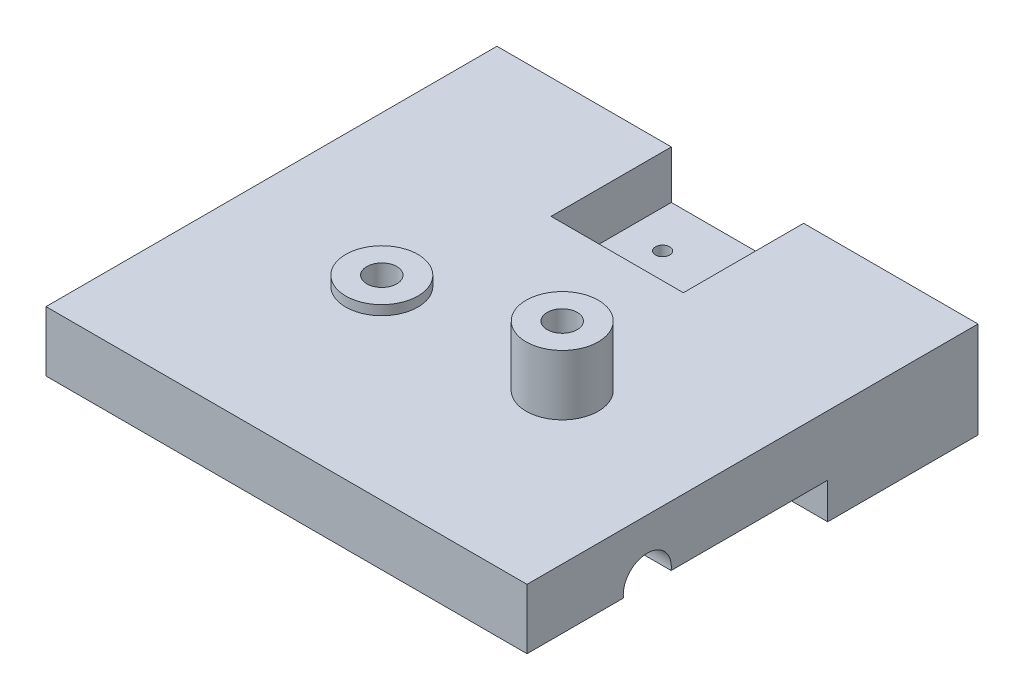
SolidWorks part; units mm, degrees
ref_plane "Front Plane" through (0, 0, 0) normal (0, 0, 1) x (1, 0, 0)
ref_plane "Top Plane" through (0, 0, 0) normal (0, 1, 0) x (1, 0, 0)
ref_plane "Right Plane" through (0, 0, 0) normal (1, 0, 0) x (0, 0, -1)
sketch "Sketch1" plane through (0, 0, 0) normal (0, 1, 0) x (1, 0, 0)
  line L1 (0, 0) -> (80, 0)
  line L2 (0, 0) -> (0, -50)
  line L3 (0, -50) -> (80, -50)
  line L4 (80, 0) -> (80, -50)
  dimension "D1" = 80
  dimension "D2" = 50
extrude "Boss-Extrude1" add sketch "Sketch1" along normal blind 10
sketch "Sketch2" plane through (0, 0, 0) normal (0, 0, 1) x (1, 0, 0)
  line L0 (0, 0) -> (80, 0) construction
  circle A0 centre (14, 0) radius 6.5
  circle A1 centre (66, 0) radius 6.5
  dimension "D1" = 13
  dimension "D2" = 13
  dimension "D3" = 14
  dimension "D4" = 14
extrude "Boss-Extrude3" add sketch "Sketch2" along normal blind 10
sketch "Sketch3" plane through (0, 0, 0) normal (0, 0, -1) x (-1, 0, 0)
  circle A0 centre (-66, 0) radius 6.5
  circle A1 centre (-14, 0) radius 6.5
extrude "Boss-Extrude4" add sketch "Sketch3" along normal blind 15
sketch "Sketch4" plane through (0, 0, -15) normal (0, 0, -1) x (-1, 0, 0)
  circle A0 centre (-14, 0) radius 3.15
  circle A1 centre (-66, 0) radius 3.15
  dimension "D1" = 6.3
  dimension "D2" = 6.3
extrude "Cut-Extrude1" cut sketch "Sketch4" against normal blind 40
sketch "Sketch5" plane through (0, 0, 0) normal (0, -1, 0) x (1, 0, 0)
  line L0 (59.5, 0) -> (20.5, 0) construction
  line L1 (0, 0) -> (0, 50) construction
  line L2 (80, 50) -> (80, 0) construction
  circle A0 centre (25, 14) radius 2.5
  circle A1 centre (55, 14) radius 2.5
  dimension "D1" = 5
  dimension "D2" = 5
  dimension "D3" = 14
  dimension "D4" = 14
  dimension "D5" = 25
  dimension "D6" = 25
ref_plane "Plane1" through (40, 0, 0) normal (-1, 0, 0) x (0, 0, 1)
sketch "Sketch6" plane through (40, 0, 0) normal (-1, 0, 0) x (0, 0, 1)
  line L0 (40, 0) -> (50, 0) construction
  line L1 (0, 0) -> (50, 0) construction
  line L2 (0, 10) -> (50, 10) construction
  line L4 (40, 10) -> (40, 0) construction
  line L5 (50, 10) -> (50, 0) construction
  line L6 (40, 1) -> (50, 1) construction
  circle A0 centre (40, 1) radius 6
  dimension "D3" = 12
  dimension "D1" = 10
  dimension "D2" = 1
extrude "Cut-Extrude3" cut sketch "Sketch6" against normal mid plane 19.5 from offset 0 contours A0
sketch "Sketch14" plane through (40, 0, 0) normal (-1, 0, 0) x (0, 0, 1)
  line L0 (10, 0) -> (56.655, 0) construction
  line L1 (50, 10) -> (50, 0) construction
  line L2 (40, 0.5) -> (55.4631, 0.5) construction
  circle A1 centre (40, 0.5) radius 4
  dimension "D1" = 8
  dimension "D2" = 10
  dimension "D3" = 0.5
extrude "Cut-Extrude4" cut sketch "Sketch14" against normal through all both and the other way through all
sketch "Sketch15" plane through (0, 0, 0) normal (0, 0, -1) x (-1, 0, 0)
  line L0 (-28.4, 10) -> (-28.4, 0) construction
  line L5 (0, 10) -> (0, 0) construction
  line L6 (-51.6, 10) -> (-51.6, 0) construction
  line L8 (-80, 10) -> (-80, 0) construction
  line L9 (-59.5, 0) -> (-20.5, 0) construction
  line L10 (-80, 10) -> (0, 10) construction
  line L11 (-51.6, 5) -> (-28.4, 5) construction
  line L12 (-51.6, 10) -> (-28.4, 10)
  line L13 (-51.6, 10) -> (-51.6, 0)
  line L14 (-51.6, 0) -> (-28.4, 0)
  line L15 (-28.4, 10) -> (-28.4, 0)
  line L16 (-50.1, 8.4) -> (-29.9, 8.4)
  line L17 (-50.1, 8.4) -> (-50.1, 1.6)
  line L18 (-50.1, 1.6) -> (-29.9, 1.6)
  line L19 (-29.9, 8.4) -> (-29.9, 1.6)
  dimension "D1" = 28.4
  dimension "D2" = 28.4
  dimension "D3" = 1.6
  dimension "D4" = 1.6
  dimension "D5" = 1.5
  dimension "D6" = 1.5
extrude "Boss-Extrude5" add sketch "Sketch15" along normal blind 15
sketch "Sketch18" plane through (0, 0, 0) normal (-1, 0, 0) x (0, 0, 1)
  line L1 (50, 10) -> (60, 10)
  line L2 (50, 10) -> (50, 0)
  line L3 (50, 0) -> (60, 0)
  line L4 (60, 10) -> (60, 0)
  dimension "D1" = 10
  dimension "D2" = 10
extrude "Boss-Extrude6" add sketch "Sketch18" against normal blind 80
sketch "Sketch19" plane through (0, 0, 0) normal (-1, 0, 0) x (0, 0, 1)
  line L6 (60, 10) -> (36.8, 10)
  line L7 (0, 10) -> (60, 10) construction
  line L8 (36.8, 10) -> (36.8, 0)
  line L9 (43.9686, 0) -> (60, 0) construction
  line L10 (36.8, 0) -> (60, 0)
  line L11 (60, 0) -> (60, 10)
  line L12 (48.4, 10) -> (48.4, 0) construction
  line L13 (36.8, 5) -> (60, 5) construction
  line L15 (38.3, 8.4) -> (58.5, 8.4)
  line L16 (38.3, 8.4) -> (38.3, 1.6)
  line L17 (38.3, 1.6) -> (58.5, 1.6)
  line L18 (58.5, 8.4) -> (58.5, 1.6)
  line L19 (38.3, 8.4) -> (58.5, 1.6) construction
  line L20 (38.3, 1.6) -> (58.5, 8.4) construction
  point P14 (48.4, 5)
  dimension "D1" = 23.2
  dimension "D2" = 20.2
  dimension "D3" = 6.8
sketch "Sketch21" plane through (0, 0, 0) normal (0, 0, -1) x (-1, 0, 0)
  line L1 (-28.4, 10) -> (0, 10)
  line L2 (-28.4, 10) -> (-28.4, -6.5346)
  line L3 (-28.4, -6.5346) -> (0, -6.5346)
  line L4 (0, 10) -> (0, -6.5346)
  circle A1 centre (-14, 0) radius 6.5
  dimension "D3" = 13
  dimension "D1" = 16.5346
  dimension "D2" = 28.4
extrude "Boss-Extrude8" add sketch "Sketch21" along normal blind 15
sketch "Sketch22" plane through (0, 0, 0) normal (0, 0, 1) x (1, 0, 0)
  line L0 (0, 0) -> (7.5, 0)
  line L1 (0, 0) -> (0, -6.5346)
  line L2 (0, -6.5346) -> (28.4, -6.5346)
  line L3 (28.4, -6.5346) -> (28.4, 0)
  line L4 (28.4, 0) -> (20.5, 0)
  arc A0 (7.5, 0) -> (20.5, 0) centre (14, 0) ccw
extrude "Boss-Extrude9" add sketch "Sketch22" along normal blind 10
sketch "Sketch23" plane through (0, 0, 0) normal (0, 0, -1) x (-1, 0, 0)
  line L0 (-80, 10) -> (-51.6, 10)
  line L1 (-51.6, 10) -> (-51.6, -6.5)
  line L2 (-51.6, -6.5) -> (-80, -6.5)
  line L3 (-80, -6.5) -> (-80, 10)
  circle A1 centre (-66, 0) radius 3.15
extrude "Boss-Extrude12" add sketch "Sketch23" along normal blind 15
sketch "Sketch24" plane through (0, 0, 0) normal (0, 0, 1) x (1, 0, 0)
  line L1 (51.6, 0) -> (59.5, 0)
  line L2 (51.6, 0) -> (51.6, -6.5)
  line L3 (51.6, -6.5) -> (80, -6.5)
  line L4 (80, -6.5) -> (80, 0)
  line L5 (80, 0) -> (72.5, 0)
  arc A0 (59.5, 0) -> (72.5, 0) centre (66, 0) ccw
  line M1 (80, 0) -> (72.5, 0)
  arc M2 (72.5, 0) -> (66, -6.5) centre (66, 0) cw
  line M3 (66, -6.5) -> (80, -6.5)
  line M4 (80, -6.5) -> (80, 0)
extrude "Boss-Extrude13" add sketch "Sketch24" along normal blind 10 contours M4 M1 M2 M3 | A0 L1 L2 L3 region at (75.4342, -3.532, 0) region at (56.3607, -3.5198, 0)
sketch "Sketch25" plane through (0, 0, 0) normal (0, -1, 0) x (1, 0, 0)
  line L0 (28.4, 10) -> (51.6, 10)
  line L1 (28.4, 10) -> (28.4, -15)
  line L2 (28.4, -15) -> (51.6, -15)
  line L3 (51.6, -15) -> (51.6, 10)
sketch "Sketch26" plane through (0, 0, 0) normal (0, 0, -1) x (-1, 0, 0)
  line L1 (-50.1, 8.4) -> (-29.9, 8.4)
  line L2 (-50.1, 8.4) -> (-50.1, 1.6)
  line L3 (-50.1, 1.6) -> (-29.9, 1.6)
  line L4 (-29.9, 8.4) -> (-29.9, 1.6)
extrude "Boss-Extrude15" add sketch "Sketch26" along normal blind 15
sketch "Sketch27" plane through (0, 0, -15) normal (0, 0, -1) x (-1, 0, 0)
  line L0 (-51, 10) -> (-40, 10)
  line L1 (-40, 10) -> (-40, 2) construction
  line L2 (-40, 10) -> (-29, 10)
  line L3 (-51, 10) -> (-51, 2)
  line L5 (-51, 2) -> (-29, 2)
  line L6 (0, 10) -> (-80, 10) construction
  line L14 (-29, 2) -> (-29, 10)
  line L15 (-40, 1.7414) -> (-40, 1.735) construction
  point P12 (-40, 1.735)
  dimension "D1" = 11
  dimension "D2" = 11
  dimension "D3" = 8
extrude "Cut-Extrude7" cut sketch "Sketch27" against normal blind 20
sketch "Sketch30" plane through (0, 2, 0) normal (0, 1, 0) x (1, 0, 0)
  line L0 (40, -5) -> (40, 15) construction
  line L1 (29, -5) -> (51, -5) construction
  line L2 (51, 15) -> (29, 15) construction
  line L3 (45, -5) -> (40, -5)
  line L6 (40, -1) -> (45, -1)
  line L7 (45, -1) -> (45, -5)
  line L8 (40, -5) -> (35, -5)
  line L9 (51, -5) -> (29, -5) construction
  line L10 (35, -5) -> (35, -1)
  line L11 (35, -1) -> (40, -1)
  dimension "D1" = 5
  dimension "D2" = 5
  dimension "D3" = 4
extrude "Cut-Extrude8" cut sketch "Sketch30" against normal blind 16
sketch "Sketch32" plane through (80, 0, 0) normal (1, 0, 0) x (0, 0, -1)
  line L0 (15, 10) -> (15, -6.5) construction
  line L3 (-60, -6) -> (15, -6)
  line L5 (15, -6) -> (15, -8.556)
  line L6 (15, -8.556) -> (-60, -8.556)
  line L7 (-60, -8.556) -> (-60, -6)
extrude "Cut-Extrude9" cut sketch "Sketch32" against normal blind 116.53
sketch "Sketch38" plane through (0, 2, 0) normal (0, 1, 0) x (1, 0, 0)
  line L0 (51, 15) -> (29, 15) construction
  line L3 (40, 15) -> (40, -1) construction
  line L4 (45, -1) -> (35, -1) construction
  circle A0 centre (35.25, 7.3) radius 1.185
  circle A1 centre (44.75, 7.3) radius 1.185
  dimension "D4" = 2.37
  dimension "D5" = 7.7
  dimension "D1" = 7.7
  dimension "D2" = 4.75
  dimension "D3" = 4.75
extrude "Cut-Extrude12" cut sketch "Sketch38" against normal blind 20
sketch "Sketch39" plane through (0, -6, 0) normal (0, -1, 0) x (1, 0, 0)
  line L0 (28.4, 10) -> (51.6, 10)
  line L1 (51.6, 10) -> (51.6, -15)
  line L2 (51.6, -15) -> (28.4, -15)
  line L3 (28.4, -15) -> (28.4, 10)
  line L4 (35, 5) -> (45, 5)
  line L5 (45, 5) -> (45, 1)
  line L6 (45, 1) -> (35, 1)
  line L7 (35, 1) -> (35, 5)
  circle A0 centre (35.25, -7.3) radius 1.185
  circle A1 centre (44.75, -7.3) radius 1.185
extrude "Boss-Extrude18" add sketch "Sketch39" against normal blind 6
sketch "Sketch40" plane through (0, 10, 0) normal (0, 1, 0) x (1, 0, 0)
  line L0 (25, -29.15) -> (55, -29.15) construction
  line L3 (0, 15) -> (29, 15) construction
  circle A0 centre (25, -29.15) radius 2.5
  circle A1 centre (55, -29.15) radius 2.5
  dimension "D1" = 5
  dimension "D2" = 5
  dimension "D3" = 44.15
  dimension "D5" = 30
extrude "Cut-Extrude13" cut sketch "Sketch40" against normal blind 20
extrude "Cut-Extrude14" cut sketch "Sketch5" against normal blind 77.25
sketch "Sketch42" plane through (0, 10, 0) normal (0, 1, 0) x (1, 0, 0)
  circle A0 centre (55, -29.15) radius 2.5
  circle A1 centre (55, -29.15) radius 6
  dimension "D1" = 12
extrude "Boss-Extrude20" add sketch "Sketch42" along normal blind 10
sketch "Sketch43" plane through (0, 10, 0) normal (0, 1, 0) x (1, 0, 0)
  circle A0 centre (25, -29.15) radius 2.5
  circle A1 centre (25, -29.15) radius 6
  dimension "D1" = 12
extrude "Boss-Extrude21" add sketch "Sketch43" along normal blind 1.6
sketch "Sketch44" plane through (0, 10, 0) normal (0, 1, 0) x (1, 0, 0)
  circle A0 centre (25, -14) radius 2.5
  circle A1 centre (55, -14) radius 2.5
extrude "Boss-Extrude22" add sketch "Sketch44" against normal blind 10
sketch "Sketch45" plane through (0, 0, 0) normal (-1, 0, 0) x (0, 0, 1)
  text T0 "29"
extrude "Cut-Extrude15" cut sketch "Sketch45" against normal blind 2
